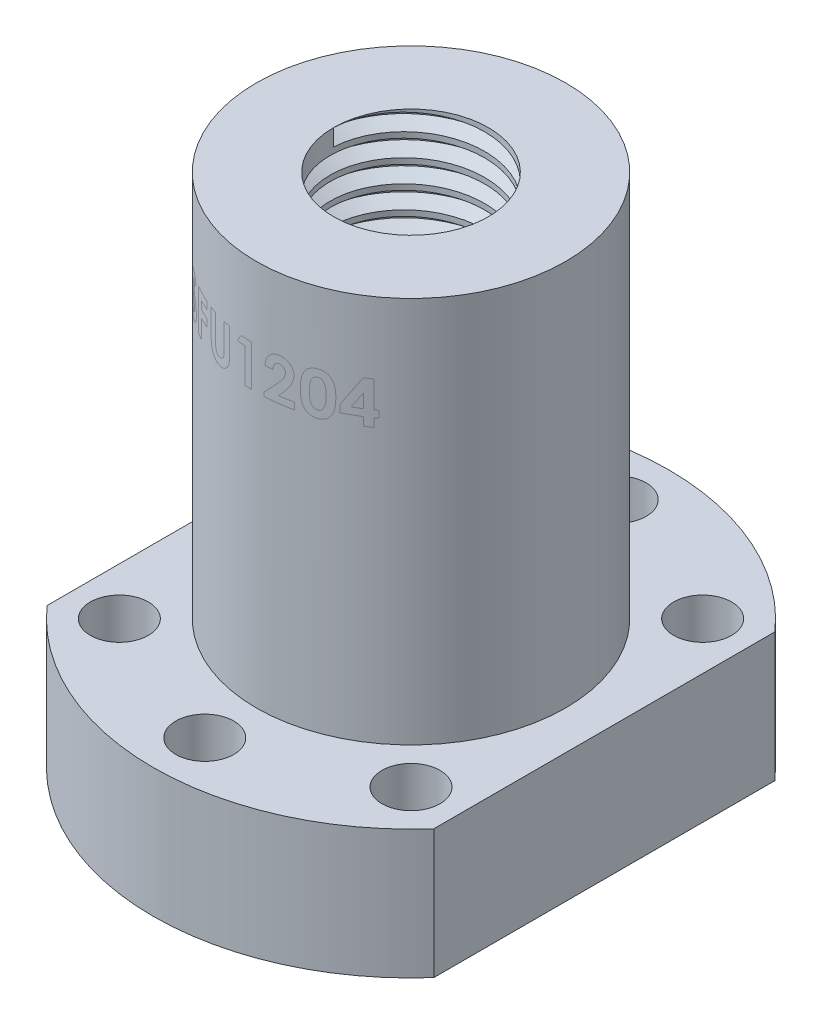
SolidWorks part; units mm, degrees
material "Copper"
ref_plane "Front Plane" through (0, 0, 0) normal (0, 0, 1) x (1, 0, 0)
ref_plane "Top Plane" through (0, 0, 0) normal (0, 1, 0) x (1, 0, 0)
ref_plane "Right Plane" through (0, 0, 0) normal (1, 0, 0) x (0, 0, -1)
sketch "Sketch1" plane through (0, 0, 0) normal (0, 1, 0) x (1, 0, 0)
  line L0 (0, 52.1095) -> (0, -46.5324) construction
  line L1 (-92.3326, 0) -> (-20, 0) construction
  line L2 (-15, 13.2288) -> (-15, -13.2288)
  line L3 (15, 13.2288) -> (15, -13.2288)
  line L4 (20, 0) -> (92.3326, 0) construction
  line L5 (-15, 0) -> (15, 0) construction
  circle A0 centre (0, 0) radius 12
  arc A1 (15, 13.2288) -> (-15, 13.2288) centre (0, 0) ccw
  arc A2 (-15, -13.2288) -> (15, -13.2288) centre (0, 0) ccw
  point P9 (0, 0)
  dimension "D1" = 24
  dimension "D2" = 40
extrude "Boss-Extrude1" add sketch "Sketch1" along normal blind 10
sketch "Sketch3" plane through (0, 10, 0) normal (0, 1, 0) x (1, 0, 0)
  line L2 (-15, 13.2288) -> (-15, -13.2288)
  line L3 (15, -13.2288) -> (15, 13.2288)
  line L4 (-15, 13.2288) -> (-15, -13.2288)
  line L5 (15, -13.2288) -> (15, 13.2288)
  arc A2 (15, 13.2288) -> (-15, 13.2288) centre (0, 0) ccw
  arc A3 (-15, -13.2288) -> (15, -13.2288) centre (0, 0) ccw
  arc A4 (15, 13.2288) -> (-15, 13.2288) centre (0, 0) ccw
  arc A5 (-15, -13.2288) -> (15, -13.2288) centre (0, 0) ccw
  circle M9 centre (0, 0) radius 12
  dimension "D1" = 0
extrude "Boss-Extrude2" add sketch "Sketch3" along normal blind 30 separate body contours M9 region at (0, 10, 0)
sketch "Sketch4" plane through (0, 40, 0) normal (0, 1, 0) x (1, 0, 0)
  circle A0 centre (0, 0) radius 6
  dimension "D1" = 12
extrude "Cut-Extrude1" cut sketch "Sketch4" against normal blind 73
sketch "Sketch6" plane through (0, 10, 0) normal (0, -1, 0) x (1, 0, 0)
  circle A1 centre (0, 0) radius 12
  circle A2 centre (0, 0) radius 12
  circle M2 centre (0, 0) radius 6
  circle M3 centre (0, 0) radius 12
  dimension "D1" = 0
extrude "Boss-Extrude4" add sketch "Sketch6" along normal up to surface (10 mm away) contours M3 M2 region at (-11.6606, 10, 0) up to face at (0, 0, 0)
sketch "Sketch9" plane through (0, 0, 0) normal (0, -1, 0) x (1, 0, 0)
  line L0 (0, 34.5699) -> (0, -34.5699) construction
  line L1 (55.9416, 0) -> (-55.9416, 0) construction
  line L2 (-26.5005, 26.5005) -> (26.5005, -26.5005) construction
  line L3 (24.3403, 24.3403) -> (-24.3403, -24.3403) construction
  circle A0 centre (0, 16) radius 2.25
  circle A2 centre (-11.3137, 11.3137) radius 2.25
  circle A4 centre (0, -16) radius 2.25
  circle A5 centre (-11.3137, -11.3137) radius 2.25
  circle A6 centre (0, 0) radius 16 construction
  circle A7 centre (11.3137, -11.3137) radius 2.25
  circle A8 centre (11.3137, 11.3137) radius 2.25
  point P5 (0, 0)
  point P9 (0, 0)
  point P14 (0, 0)
  point P17 (0, 0)
  dimension "D3" = 4.5
  dimension "D4" = 32
  dimension "D1" = 45
  dimension "D2" = 45
extrude "Cut-Extrude2" cut sketch "Sketch9" against normal blind 65 contours A0 | A8 | A2 | A5 | A4 | A7 | A2 | A0 region at (0, 0, 16) region at (-11.3137, 0, 11.3137) region at (0, 0, -16) region at (-11.3137, 0, -11.3137) region at (11.3137, 0, -11.3137) region at (11.3137, 0, 11.3137)
sketch "Sketch10" plane through (0, 0, 0) normal (0, -1, 0) x (1, 0, 0)
  line L0 (15.3516, -37.062) -> (-15.3516, 37.062) construction
  line L2 (0, 34.5699) -> (0, -34.5699) construction
  point P4 (0, 0)
  dimension "D1" = 22.5
sketch "Sketch11" plane through (0, 0, 0) normal (0, 0, 1) x (1, 0, 0)
  line L0 (15.3516, 0) -> (-15.3516, 0) construction
  line L1 (15.3516, 0) -> (-15.3516, 0)
  line L4 (15.3516, 0) -> (-15.3516, 0)
sketch "Sketch12" plane through (0, 0, 0) normal (0, -1, 0) x (1, 0, 0)
  arc A1 (15, 13.2288) -> (-15, 13.2288) centre (0, 0) ccw construction
  arc A2 (15, 13.2288) -> (-15, 13.2288) centre (0, 0) ccw
  point P3 (0, 0)
ref_plane "Plane2" through (0, 5, 0) normal (0, -1, 0) x (-1, 0, 0)
sketch "Sketch13" plane through (0, 5, 0) normal (0, -1, 0) x (-1, 0, 0)
  line L0 (0, -34.5699) -> (0, 34.5699) construction
  line L1 (-15.3516, 37.062) -> (15.3516, -37.062) construction
  line L2 (0, -34.5699) -> (0, 34.5699)
  line L3 (-15.3516, 37.062) -> (15.3516, -37.062)
ref_plane "Plane3" through (-7.6537, 0, 18.4776) normal (0.3827, 0, -0.9239) x (-0.9239, 0, -0.3827)
sketch "Sketch16" plane through (-7.6537, 0, 18.4776) normal (0.3827, 0, -0.9239) x (-0.9239, 0, -0.3827)
  circle A0 centre (0, 5) radius 3.1
  point P0 (0, 5)
  dimension "D1" = 6.2
thread "Thread2" pitch 1.75 method cut profile "Thread Profile2" start angle 0, offset 0, length 0, pitch 1.75, diameter 12
ref_plane "Plane4" through (-6, 40, 0) normal (0, 0, 1) x (-1, 0, 0)
sketch "Thread Profile2" plane through (-6, 40, 0) normal (0, 0, 1) x (-1, 0, 0)
  line L0 (0, 0) -> (0, 1.75) construction
  line L1 (0, 0) -> (0.9472, 0.5469)
  line L2 (0.9472, 0.5469) -> (0.9472, 0.7656)
  line L3 (0.9472, 0.7656) -> (0, 1.3125)
  line L4 (0.9472, 0.6562) -> (0, 0.6562) construction
  line L11 (0, 0) -> (0, 1.3125)
  point P2 (0, 0)
  dimension "Pitch" = 1.75
  dimension "Profile_Angle" = 60
  dimension "Profile_Land" = 0.2188
  dimension "Profile_Height" = 0.9472
sketch "Sketch20" plane through (0, 0, 0) normal (0, 0, 1) x (1, 0, 0)
  text T0 "<b>SFU1204</b>"
wrap "Wrap1" sketch "Sketch20" wrap type scribe source sketch "Sketch20" face at (0, 40, 12)
